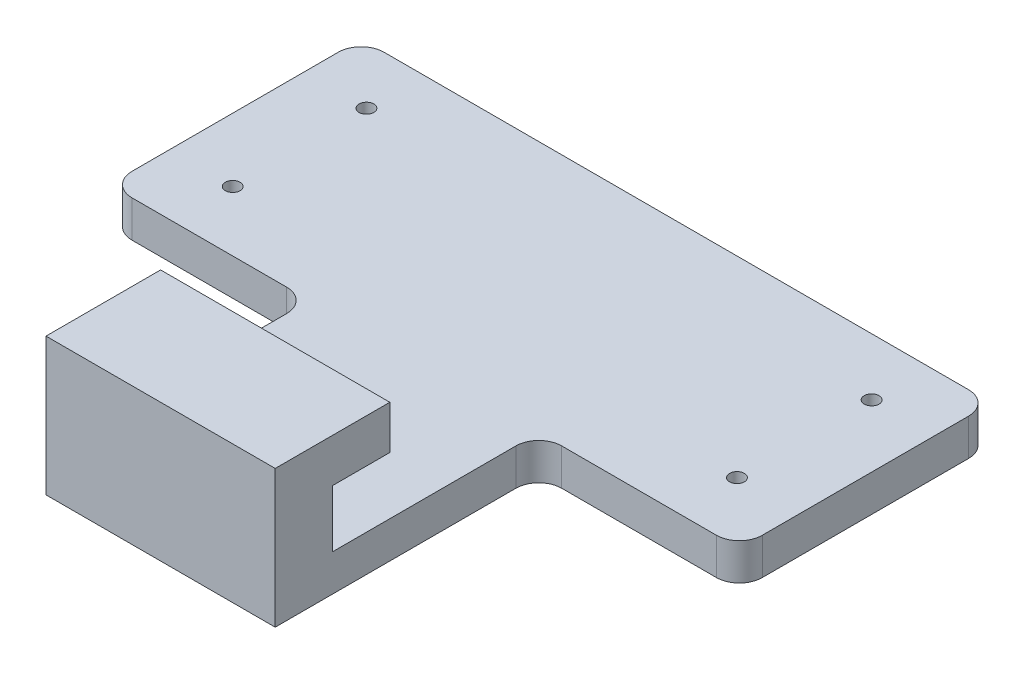
SolidWorks part; units mm, degrees
ref_plane "Front Plane" through (0, 0, 0) normal (0, 0, 1) x (1, 0, 0)
ref_plane "Top Plane" through (0, 0, 0) normal (0, 1, 0) x (1, 0, 0)
ref_plane "Right Plane" through (0, 0, 0) normal (1, 0, 0) x (0, 0, -1)
sketch "Sketch1" plane through (0, 0, 0) normal (0, 1, 0) x (1, 0, 0)
  line L1 (-34.925, -28.575) -> (34.925, -28.575)
  line L2 (-34.925, -28.575) -> (-34.925, 28.575)
  line L3 (-34.925, 28.575) -> (34.925, 28.575)
  line L4 (34.925, -28.575) -> (34.925, 28.575)
  line L5 (-34.925, -28.575) -> (34.925, 28.575) construction
  line L6 (-34.925, 28.575) -> (34.925, -28.575) construction
  point P0 (0, 0)
  dimension "D1" = 57.15
  dimension "D2" = 69.85
extrude "Boss-Extrude1" add sketch "Sketch1" along normal blind 15.24
sketch "Sketch2" plane through (-34.925, 0, 0) normal (-1, 0, 0) x (0, 0, 1)
  line L0 (-28.575, 15.24) -> (-28.575, 0) construction
  line L1 (-28.575, 10.414) -> (22.225, 10.414)
  line L2 (-28.575, 10.414) -> (-28.575, 4.064)
  line L3 (-28.575, 4.064) -> (22.225, 4.064)
  line L4 (22.225, 10.414) -> (22.225, 4.064)
  dimension "D1" = 6.35
  dimension "D2" = 50.8
  dimension "D3" = 4.064
extrude "Cut-Extrude1" cut sketch "Sketch2" against normal up to surface (69.85 mm away) up to face at (34.925, 7.62, 0)
sketch "Sketch3" plane through (-34.925, 0, 0) normal (-1, 0, 0) x (0, 0, 1)
  line L0 (22.225, 10.414) -> (-28.575, 10.414) construction
  line L1 (-28.575, 15.24) -> (15.875, 15.24)
  line L2 (-28.575, 15.24) -> (-28.575, 10.414)
  line L3 (-28.575, 10.414) -> (15.875, 10.414)
  line L4 (15.875, 15.24) -> (15.875, 10.414)
  dimension "D1" = 44.45
extrude "Cut-Extrude2" cut sketch "Sketch3" against normal blind 50.8
mirror "Mirror1" about plane through (0, 0, 0) normal (1, 0, 0) of "Cut-Extrude2"
sketch "Sketch5" plane through (0, 0, 0) normal (0, -1, 0) x (1, 0, 0)
  line L0 (-27.9908, -22.225) -> (27.9908, -22.225) construction
  line L3 (-30.861, -4.765) -> (30.861, -4.765)
  line L4 (-30.861, -4.765) -> (-30.861, -24.765)
  line L5 (-30.861, -24.765) -> (30.861, -24.765)
  line L6 (30.861, -4.765) -> (30.861, -24.765)
  line L7 (34.925, -28.575) -> (-34.925, -28.575) construction
  line L8 (-27.8892, -7.305) -> (27.9908, -7.305) construction
  circle A0 centre (-27.9908, -22.225) radius 0.8192
  circle A1 centre (27.9908, -22.225) radius 0.8192
  circle A2 centre (-27.8892, -7.305) radius 0.8191
  circle A3 centre (27.9908, -7.305) radius 0.8192
  point P0 (-27.9908, -22.225)
  point P1 (27.9908, -22.225)
  point P2 (0, -22.225)
  point P3 (-30.861, 12.0482)
  point P12 (0, -24.765)
  point P14 (0, 0)
  point P16 (0, 0)
  point P17 (-27.8892, -7.305)
  point P18 (0, -24.765)
  point P20 (27.9908, -7.305)
  point P26 (0, 0)
  point P27 (0, 0)
  point P28 (-29.0264, -7.305)
  point P29 (0, 0)
  point P30 (-23.2903, -7.305)
  line M3 (34.925, 28.575) -> (-34.925, 28.575)
  dimension "D5" = 1.6383
  dimension "D6" = 1.6383
  dimension "D9" = 1.6383
  dimension "D10" = 1.6383
  dimension "D1" = 2.54
  dimension "D2" = 55.9816
  dimension "D3" = 20
  dimension "D4" = 61.722
  dimension "D7" = 3.81
  dimension "D8" = 2.54
  dimension "D11" = 55.88
extrude "Cut-Extrude3" cut sketch "Sketch5" against normal blind 1.016 contours L6 L4 L5 A0 A1 M3 | A0 | A1 region at (-0.0002, 0, -14.765) region at (-27.9908, 0, -22.225) region at (27.9908, 0, -22.225)
extrude "Cut-Extrude4" cut sketch "Sketch5<3>" against normal through all contours A0 | A1 | A2 | A3 region at (-27.9908, 0, -22.225) region at (27.9908, 0, -22.225) region at (-27.8892, 0, -7.305)
sketch "Sketch5<3>" plane through (0, 0, 0) normal (0, -1, 0) x (1, 0, 0) same geometry as "Sketch5"
sketch "Sketch7" plane through (0, 0, 22.225) normal (0, 0, -1) x (-1, 0, 0)
  line L0 (-34.925, 15.24) -> (34.925, 15.24) construction
  line L1 (-34.925, 9.144) -> (34.925, 9.144)
  line L2 (-34.925, 9.144) -> (-34.925, 15.24)
  line L3 (-34.925, 15.24) -> (34.925, 15.24)
  line L4 (34.925, 9.144) -> (34.925, 15.24)
  line L5 (-34.925, 9.144) -> (34.925, 15.24) construction
  line L6 (-34.925, 15.24) -> (34.925, 9.144) construction
  line L7 (-34.925, 4.064) -> (34.925, 4.064) construction
  point P0 (0, 12.192)
  point P5 (34.925, 13.7211)
  point P6 (0, 0)
  point P7 (0, 0)
  dimension "D1" = 5.08
  dimension "D2" = 69.85
extrude "Boss-Extrude2" add sketch "Sketch7" along normal blind 6.35
sketch "Sketch8" plane through (-34.925, 0, 0) normal (-1, 0, 0) x (0, 0, 1)
  line L0 (15.875, 10.414) -> (22.225, 10.414)
  line L1 (15.875, 9.144) -> (15.875, 15.24) construction
  line L3 (15.875, 9.144) -> (22.225, 9.144) construction
  line L5 (22.225, 9.144) -> (22.225, 4.064) construction
  line L6 (15.875, 10.414) -> (15.875, 9.144)
  line L7 (15.875, 9.144) -> (22.225, 9.144)
  line L8 (22.225, 9.144) -> (22.225, 10.414)
  dimension "D1" = 1.27
  dimension "D2" = 1.27
extrude "Cut-Extrude9" cut sketch "Sketch8" against normal through all both and the other way through all
sketch "Sketch17" plane through (0, 0, 15.875) normal (0, 0, -1) x (-1, 0, 0)
  line L0 (-34.925, 15.24) -> (34.925, 15.24) construction
  line L1 (-12.7, 15.24) -> (12.7, 15.24)
  line L2 (-12.7, 15.24) -> (-12.7, 10.414)
  line L3 (-12.7, 10.414) -> (12.7, 10.414)
  line L4 (12.7, 15.24) -> (12.7, 10.414)
  line L7 (-12.7, 15.24) -> (-34.925, 15.24)
  line L8 (-12.7, 15.24) -> (-12.7, 10.414)
  line L9 (-12.7, 10.414) -> (-34.925, 10.414)
  line L10 (-34.925, 15.24) -> (-34.925, 10.414)
  line L11 (12.7, 15.24) -> (34.925, 15.24)
  line L12 (12.7, 15.24) -> (12.7, 10.414)
  line L13 (12.7, 10.414) -> (34.925, 10.414)
  line L14 (34.925, 15.24) -> (34.925, 10.414)
  line L16 (-34.925, 10.414) -> (-34.925, 15.24) construction
  line L17 (34.925, 10.414) -> (34.925, 15.24) construction
  line L18 (-34.925, 10.414) -> (34.925, 10.414) construction
  point P4 (0, 0)
  point P5 (0, 0)
  point P6 (0, 0)
  point P7 (0, 0)
  point P13 (0, 15.24)
  point P16 (0, 0)
  point P19 (0, 0)
  point P20 (0, 0)
  point P21 (0, 0)
  point P28 (0, 0)
  line M4 (-34.925, 15.24) -> (-34.925, 10.414)
  line M5 (-34.925, 10.414) -> (34.925, 10.414)
  line M6 (34.925, 10.414) -> (34.925, 15.24)
  dimension "D1" = 25.4
extrude "Cut-Extrude13" cut sketch "Sketch17" against normal up to surface (6.35 mm away) contours L2 M4 M5 | L4 M5 M6 region at (23.8125, 12.827, 15.875) region at (-23.8125, 12.827, 15.875) up to face at (0, 7.239, 22.225)
sketch "Sketch18" plane through (0, 15.24, 0) normal (0, 1, 0) x (1, 0, 0)
  line L0 (-12.7, -22.225) -> (-12.7, -15.875) construction
  line L1 (-34.925, -28.575) -> (-12.7, -28.575)
  line L2 (-34.925, -28.575) -> (-34.925, 0.635)
  line L3 (-34.925, 0.635) -> (-12.7, 0.635)
  line L4 (-12.7, -28.575) -> (-12.7, 0.635)
  line L5 (12.7, -22.225) -> (12.7, -15.875) construction
  line L6 (34.925, -28.575) -> (12.7, -28.575)
  line L7 (34.925, -28.575) -> (34.925, 0.635)
  line L8 (34.925, 0.635) -> (12.7, 0.635)
  line L9 (12.7, -28.575) -> (12.7, 0.635)
  dimension "D1" = 29.21
extrude "Cut-Extrude14" cut sketch "Sketch18" against normal through all both and the other way through all
fillet "Fillet1" radius 2.54 6 edges at (-34.925, 2.032, -0.635) (-34.925, 2.032, -28.575) (34.925, 2.032, -28.575) (34.925, 2.032, -0.635) (12.7, 2.032, -0.635) (-12.7, 2.032, -0.635)
